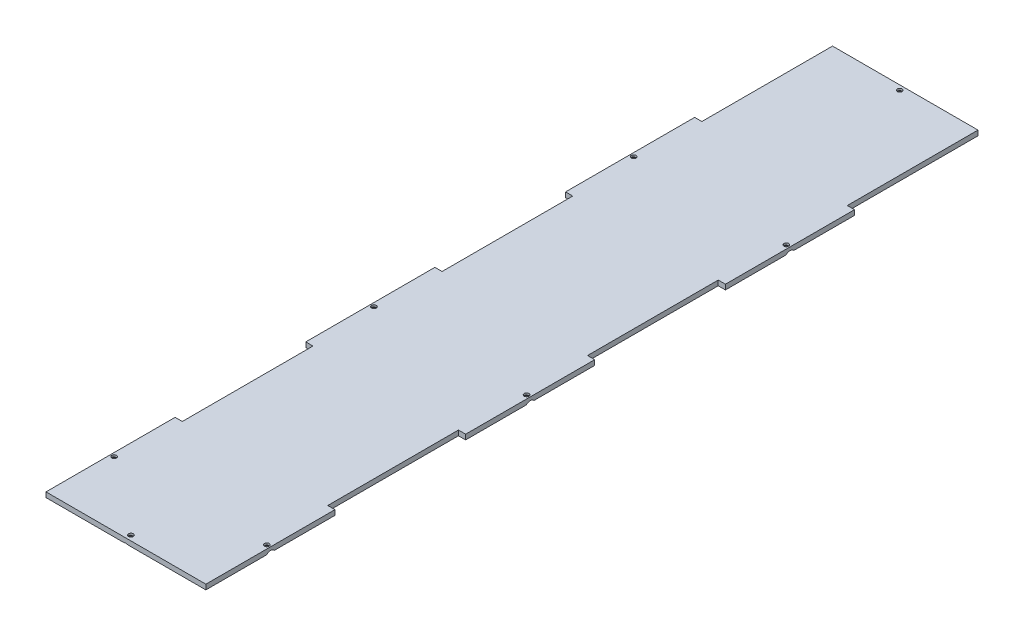
SolidWorks part; units mm, degrees
ref_plane "Front Plane" through (0, 0, 0) normal (0, 0, 1) x (1, 0, 0)
ref_plane "Top Plane" through (0, 0, 0) normal (0, 1, 0) x (1, 0, 0)
ref_plane "Right Plane" through (0, 0, 0) normal (1, 0, 0) x (0, 0, -1)
sketch "Sketch1" plane through (0, 0, 0) normal (0, 1, 0) x (1, 0, 0)
  line L1 (-167.5421, -181.5557) -> (-167.5421, -149.0446) construction
  line L2 (-121.3141, -99.5137) -> (-116.7421, -99.5137) construction
  line L3 (-116.6913, -99.5137) -> (-116.7421, -99.5137) construction
  line L4 (-121.3141, -16.4557) -> (-116.7421, -16.4557) construction
  line L5 (-117.3771, -16.4557) -> (-116.7421, -16.4557) construction
  line L6 (-121.3141, 65.5863) -> (-116.7421, 65.5863) construction
  line L7 (-117.3771, 65.5863) -> (-116.7421, 65.5863) construction
  line L8 (-117.3771, 148.6443) -> (-116.7421, 148.6443) construction
  line L9 (-117.3771, 148.6443) -> (-116.7421, 148.6443) construction
  line L10 (-121.3141, 230.6863) -> (-116.7421, 230.6863) construction
  line L11 (-117.3771, 230.6863) -> (-116.7421, 230.6863) construction
  line L12 (-116.7421, 65.5863) -> (-116.7421, -16.4557)
  line L13 (-121.3141, 307.3943) -> (-121.3141, 230.6863)
  line L14 (-121.3141, -181.5557) -> (-213.7701, -181.5557)
  line L15 (-116.7421, -16.4557) -> (-121.3141, -16.4557)
  line L16 (-121.3141, 230.6863) -> (-116.7421, 230.6863)
  line L17 (-213.7701, 307.3943) -> (-213.7701, 313.7443)
  line L18 (-121.3141, 65.5863) -> (-116.7421, 65.5863)
  line L19 (-116.7421, 230.6863) -> (-116.7421, 148.6443)
  line L20 (-213.7701, 65.5863) -> (-218.3421, 65.5863) construction
  line L21 (-121.3141, 148.6443) -> (-121.3141, 65.5863)
  line L22 (-121.3141, -16.4557) -> (-121.3141, -99.5137)
  line L23 (-121.3141, -99.5137) -> (-116.7421, -99.5137)
  line L24 (-116.7421, -99.5137) -> (-116.7421, -181.5557)
  line L25 (-116.7421, -181.5557) -> (-121.3141, -181.5557)
  line L26 (-121.3141, 65.5863) -> (-116.7421, 65.5863) construction
  line L27 (-217.7071, 230.6863) -> (-218.3421, 230.6863) construction
  line L28 (-116.7421, 148.6443) -> (-121.3141, 148.6443)
  line L29 (-213.7701, 230.6863) -> (-218.3421, 230.6863) construction
  line L30 (-217.7071, 148.6443) -> (-218.3421, 148.6443) construction
  line L31 (-217.7071, 148.6443) -> (-218.3421, 148.6443) construction
  line L32 (-217.7071, 65.5863) -> (-218.3421, 65.5863) construction
  line L33 (-213.7701, 65.5863) -> (-218.3421, 65.5863) construction
  line L34 (-217.7071, -16.4557) -> (-218.3421, -16.4557) construction
  line L35 (-213.7701, -16.4557) -> (-218.3421, -16.4557) construction
  line L36 (-219.4851, -99.5137) -> (-218.3421, -99.5137) construction
  line L37 (-213.7701, -99.5137) -> (-218.3421, -99.5137) construction
  line L38 (-218.3421, -181.5557) -> (-213.7701, -181.5557)
  line L39 (-218.3421, -99.5137) -> (-218.3421, -181.5557)
  line L40 (-213.7701, -99.5137) -> (-218.3421, -99.5137)
  line L41 (-213.7701, -16.4557) -> (-213.7701, -99.5137)
  line L42 (-213.7701, 148.6443) -> (-213.7701, 65.5863)
  line L43 (-218.3421, 230.6863) -> (-218.3421, 148.6443)
  line L44 (-213.7701, 65.5863) -> (-218.3421, 65.5863)
  line L45 (-213.7701, 313.7443) -> (-121.3141, 313.7443)
  line L46 (-213.7701, 230.6863) -> (-218.3421, 230.6863)
  line L47 (-213.7701, -16.4557) -> (-218.3421, -16.4557)
  line L48 (-213.7701, 307.3943) -> (-213.7701, 230.6863)
  line L49 (-218.3421, 65.5863) -> (-218.3421, -16.4557)
  line L50 (-218.3421, 148.6443) -> (-213.7701, 148.6443)
  line L51 (-121.3141, 313.7443) -> (-121.3141, 307.3943)
  circle A0 centre (-119.0281, 189.6653) radius 1.524
  circle A1 centre (-119.0281, 24.5653) radius 1.524
  circle A2 centre (-119.0281, -140.5347) radius 1.524
  circle A3 centre (-216.0561, 189.6653) radius 1.524
  circle A4 centre (-216.0561, 24.5653) radius 1.524
  circle A5 centre (-216.0561, -140.5347) radius 1.524
  circle A6 centre (-167.5421, -178.3807) radius 1.524
  point P39 (-167.5421, -181.5557)
  dimension "D8" = 50.8
  dimension "D12" = 3.048
  dimension "D2" = 4.572
  dimension "D3" = 4.572
  dimension "D4" = 4.572
  dimension "D5" = 82.042
  dimension "D6" = 82.042
  dimension "D7" = 82.042
  dimension "D9" = 6.35
  dimension "D13" = 3.175
  dimension "D14" = 101.6
extrude "Boss-Extrude1" add sketch "Sketch1" along normal blind 3.175
sketch "Sketch2" plane through (0, 0, 0) normal (0, -1, 0) x (1, 0, 0)
  line L3 (-213.7701, -313.7443) -> (-213.7701, -230.6863) construction
  line L4 (-121.3141, -230.6863) -> (-121.3141, -313.7443) construction
  line L5 (-213.7701, -307.9579) -> (-121.3141, -307.9579) construction
  line L6 (-121.3141, -313.7443) -> (-213.7701, -313.7443) construction
  circle A0 centre (-168.0882, -310.8233) radius 1.524
  point P11 (-170.9311, -298.9255)
  dimension "D1" = 3.048
  dimension "D2" = 45.6819
  dimension "D3" = 2.921
extrude "Cut-Extrude1" cut sketch "Sketch2" against normal blind 12.7
chamfer "Chamfer1" distance 1.905 angle 45 8 edges at (-167.5421, 0, 179.9047) (-216.0561, 0, 139.0107) (-216.0561, 0, -191.1893) (-216.0561, 0, -26.0893) (-168.0882, 0, -312.3473) (-119.0281, 0, 142.0587) (-119.0281, 0, -188.1413) (-119.0281, 0, -23.0413)
